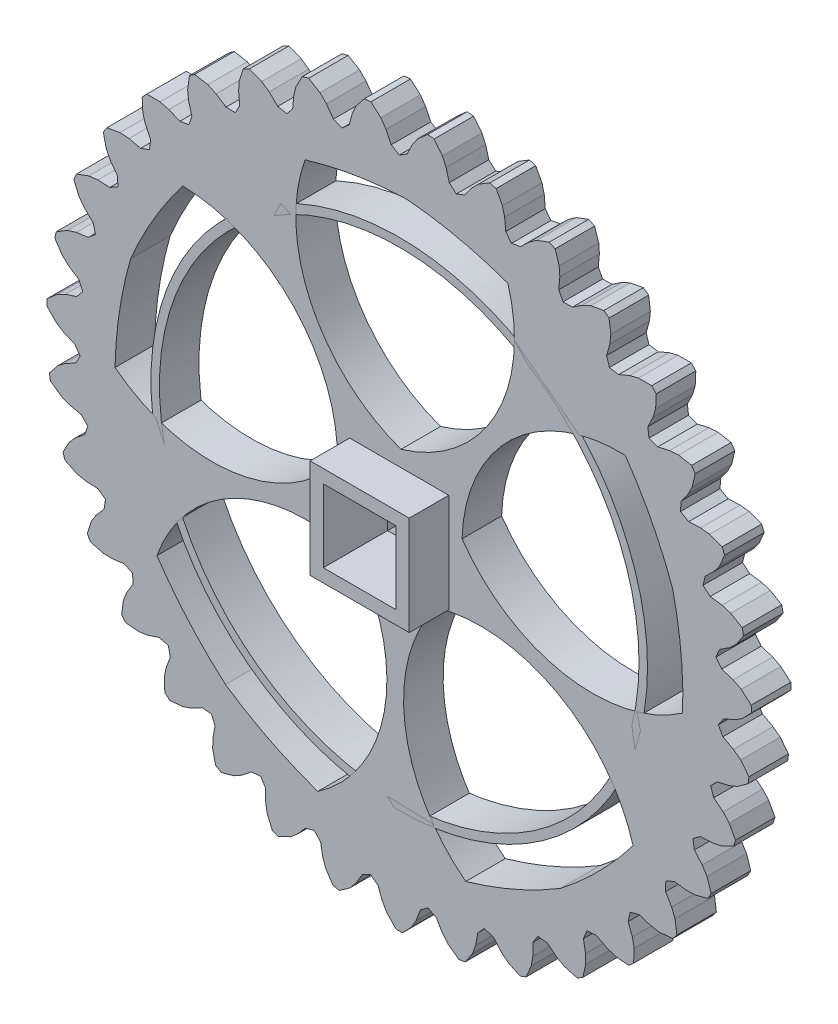
SolidWorks part; units mm, degrees
ref_plane "Front Plane" through (0, 0, 0) normal (0, 0, 1) x (1, 0, 0)
ref_plane "Top Plane" through (0, 0, 0) normal (0, 1, 0) x (1, 0, 0)
ref_plane "Right Plane" through (0, 0, 0) normal (1, 0, 0) x (0, 0, -1)
sketch "Sketch1" plane through (0, 0, 0) normal (0, 0, 1) x (1, 0, 0)
  line L1 (3.675, -3.675) -> (-3.675, -3.675)
  line L2 (3.675, -3.675) -> (3.675, 3.675)
  line L3 (3.675, 3.675) -> (-3.675, 3.675)
  line L4 (-3.675, -3.675) -> (-3.675, 3.675)
  circle A0 centre (0, 0) radius 35.65
  point P3 (0, 3.675)
  point P9 (-3.675, 0)
  dimension "D1" = 71.3
  dimension "D2" = 7.35
  dimension "D3" = 7.35
extrude "Boss-Extrude1" add sketch "Sketch1" along normal blind 4
sketch "Sketch2" plane through (0, 0, 0) normal (0, 0, 1) x (1, 0, 0)
  line L0 (0, 0) -> (0, 36.903) construction
  line L1 (0, 32.3049) -> (-0.8069, 32.8033)
  line L2 (-0.8069, 32.8033) -> (-1.33, 33.8931)
  line L3 (-1.33, 33.8931) -> (-1.8557, 34.6487)
  line L4 (-1.8557, 34.6487) -> (-2.8665, 35.5346)
  line L5 (-2.8665, 35.5346) -> (-1.8557, 36.3071)
  line L6 (-1.8557, 36.3071) -> (0, 36.903)
  line L7 (1.8557, 36.3071) -> (0, 36.903)
  line L8 (2.8665, 35.5346) -> (1.8557, 36.3071)
  line L9 (1.8557, 34.6487) -> (2.8665, 35.5346)
  line L10 (1.33, 33.8931) -> (1.8557, 34.6487)
  line L11 (0.8069, 32.8033) -> (1.33, 33.8931)
  line L12 (0, 32.3049) -> (0.8069, 32.8033)
  circle A22 centre (0, 0) radius 35.65 construction
  dimension "D5" = 0.5258
  dimension "D6" = 0.7556
  dimension "D9" = 0.5959
  dimension "D1" = 0.8069
  dimension "D2" = 0.4984
  dimension "D3" = 0.5231
  dimension "D4" = 1.0898
  dimension "D7" = 0.8858
  dimension "D8" = 1.8557
  dimension "D10" = 1.0107
  dimension "D11" = 0.7725
  dimension "D12" = 1.0107
extrude "Cut-Extrude1" cut sketch "Sketch2" along normal through all
pattern_circular "CirPattern1" count 35 over 360 about axis through (0, 0, 4) along (0, 0, -1) of "Cut-Extrude1"
sketch "Sketch3" plane through (0, 0, 0) normal (0, 0, 1) x (1, 0, 0)
  circle A0 centre (0, 0) radius 29.75
  dimension "D1" = 59.5
sketch "Sketch4" plane through (0, 0, 0) normal (0, 0, 1) x (1, 0, 0)
  line L0 (0, 0) -> (0.7854, 28.8152) construction
  arc A1 (0.7854, 28.8152) -> (-9.5267, 27.1273) centre (2.0438, -11.2177) ccw
  arc A2 (0.7854, 28.8152) -> (10.9903, 26.5681) centre (-2.6519, -11.0897) cw
  arc A4 (0.1805, 6.623) -> (-9.5267, 27.1273) centre (5.5791, 21.7288) cw
  arc A5 (0.1805, 6.623) -> (10.9903, 26.5681) centre (-4.3872, 22.0004) ccw
extrude "Cut-Extrude2" cut sketch "Sketch4" along normal through all both
sketch "Sketch5" plane through (0, 0, 0) normal (0, 0, 1) x (1, 0, 0)
  circle A0 centre (0, 0) radius 25.1098
  circle A1 centre (0, 0) radius 24.2496
extrude "Boss-Extrude2" add sketch "Sketch5" along normal through all separate body
pattern_circular "CirPattern2" count 5 over 360 about axis through (0, 0, 4) along (0, 0, -1) of "Cut-Extrude2" reverse direction yes
chamfer "Chamfer1" distance 1.5 distance2 0.5 4 edges at (-3.675, 0, 0) (0, -3.675, 0) (3.675, 0, 0) (0, 3.675, 0) first distance on face at (-3.675, 0, 2) first distance on face at (0, -3.675, 2) first distance on face at (3.675, 0, 2) first distance on face at (0, 3.675, 2)
sketch "Sketch6" plane through (0, 0, 4) normal (0, 0, 1) x (1, 0, 0)
  line L1 (-3.675, 3.675) -> (3.675, 3.675)
  line L2 (-3.675, 3.675) -> (-3.675, -3.675)
  line L3 (-3.675, -3.675) -> (3.675, -3.675)
  line L4 (3.675, 3.675) -> (3.675, -3.675)
  line L5 (-5.0131, 5.0131) -> (5.0131, 5.0131)
  line L6 (-5.0131, 5.0131) -> (-5.0131, -5.0131)
  line L7 (-5.0131, -5.0131) -> (5.0131, -5.0131)
  line L8 (5.0131, 5.0131) -> (5.0131, -5.0131)
  dimension "D1" = 1.3381
  dimension "D2" = 1.3381
  dimension "D3" = 1.3381
  dimension "D4" = 1.3381
extrude "Boss-Extrude3" add sketch "Sketch6" along normal blind 4
equation "\"padding\"=1.33807"
equation "\"D1@Sketch6\"=\"padding\""
equation "\"D2@Sketch6\"=\"padding\""
equation "\"D3@Sketch6\"=\"padding\""
equation "\"D4@Sketch6\"=\"padding\""
